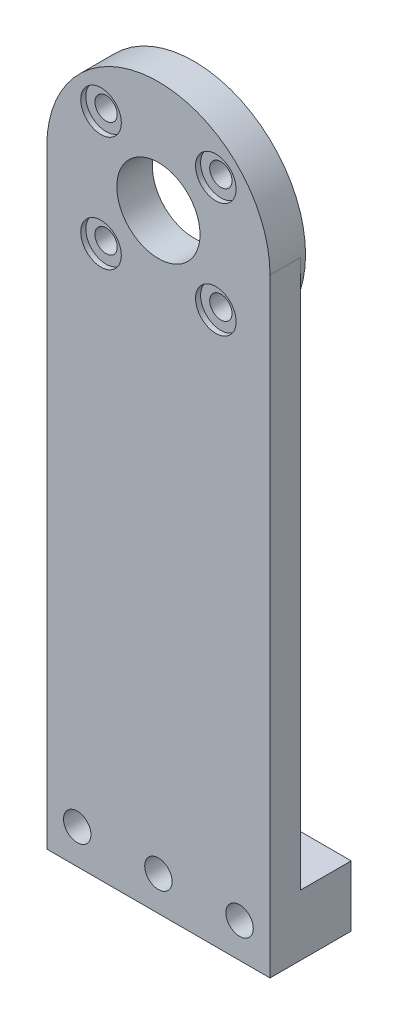
SolidWorks part; units mm, degrees
ref_plane "Front Plane" through (0, 0, 0) normal (0, 0, 1) x (1, 0, 0)
ref_plane "Top Plane" through (0, 0, 0) normal (0, 1, 0) x (1, 0, 0)
ref_plane "Right Plane" through (0, 0, 0) normal (1, 0, 0) x (0, 0, -1)
sketch "Sketch1" plane through (0, 0, 0) normal (0, 0, 1) x (1, 0, 0)
  line L0 (0, 30) -> (0, -30) construction
  line L2 (11, 30) -> (11, -30)
  line L4 (-11, 30) -> (-11, -30)
  line L5 (-11, -30) -> (11, -30)
  line L7 (11, -30) -> (-11, -30)
  line L8 (11, -30) -> (11, -24)
  line L9 (11, -24) -> (-11, -24)
  line L10 (-11, -30) -> (-11, -24)
  circle A0 centre (0, 30) radius 11
  point P0 (0, 0)
  point P2 (0, 0)
  point P8 (0, -30)
  dimension "D3" = 22
  dimension "D1" = 60
  dimension "D4" = 6
  dimension "D2" = 22
extrude "Boss-Extrude1" add sketch "Sketch1" along normal blind 3 contours L2 A0 L4 | A0 | A0 L0 L2 | L8 L7 L10 L9 region at (5.6584, -1.2532, 0) region at (-5.6584, -1.2532, 0) region at (-7.5582, 22.4418, 0)
extrude "Boss-Extrude2" add sketch "Sketch1<3>" against normal blind 0.5 contours A0 region at (0, 30, 0)
sketch "Sketch1<3>" plane through (0, 0, 0) normal (0, 0, 1) x (1, 0, 0) same geometry as "Sketch1"
sketch "Sketch2" plane through (0, 0, 3) normal (0, 0, 1) x (1, 0, 0)
  line L0 (0, 30) -> (5.6569, 35.6569) construction
  line L1 (11, 30) -> (11, -30) construction
  circle A0 centre (0, 30) radius 4.1
  circle A1 centre (5.6569, 35.6569) radius 1.1
  circle A2 centre (5.6569, 35.6569) radius 2
  dimension "D1" = 8.2
  dimension "D2" = 2.2
  dimension "D5" = 4
  dimension "D3" = 8
  dimension "D4" = 45
extrude "Cut-Extrude1" cut sketch "Sketch2" against normal up to surface (3.5 mm away) contours A0 | A1 region at (0, 30, 3) region at (5.6569, 35.6569, 3) up to face at (11, 30, -0.5)
extrude "Cut-Extrude2" cut sketch "Sketch2<3>" against normal offset from surface (0.5 mm away) 3 contours A2 A1 region at (3.7134, 35.6569, 3) up to face at (4.1, 30, -0.5)
sketch "Sketch2<3>" plane through (0, 0, 3) normal (0, 0, 1) x (1, 0, 0) same geometry as "Sketch2"
pattern_circular "CirPattern2" count 4 over 360 about axis through (0, 30, 3) along (0, 0, 1) of "Cut-Extrude2", "Cut-Extrude1"
extrude "Boss-Extrude3" add sketch "Sketch1<6>" against normal blind 5 contours L0 L9 L4 L5 | L9 L0 L7 L2 region at (5.5, -27, 0) region at (-5.5, -27, 0)
sketch "Sketch1<6>" plane through (0, 0, 0) normal (0, 0, 1) x (1, 0, 0) same geometry as "Sketch1"
sketch "Sketch4" plane through (0, 0, 3) normal (0, 0, 1) x (1, 0, 0)
  line L0 (-11, -30) -> (11, -30) construction
  circle A0 centre (0, -26.6) radius 1.35
  dimension "D2" = 2.7
  dimension "D1" = 3.4
extrude "Cut-Extrude4" cut sketch "Sketch4" against normal up to surface (8 mm away) up to face at (0, -27, -5)
pattern_linear "LPattern2" count 2 spacing 8 along (1, 0, 0) count 2 spacing 8 along (-1, 0, 0) of "Cut-Extrude4"
